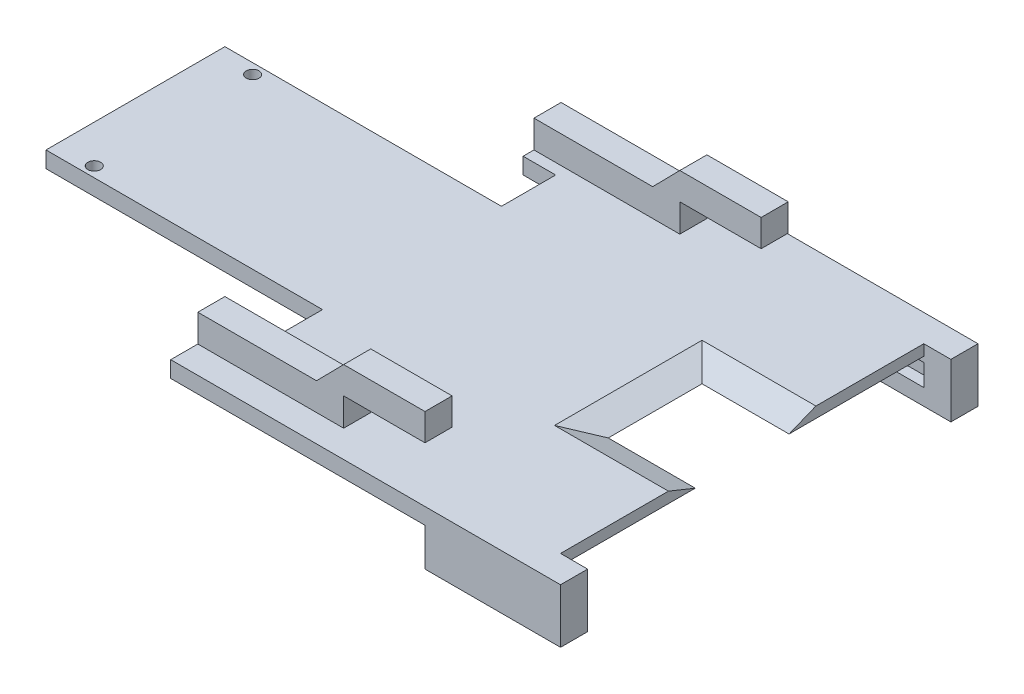
SolidWorks part; units mm, degrees
ref_plane "Front Plane" through (0, 0, 0) normal (0, 0, 1) x (1, 0, 0)
ref_plane "Top Plane" through (0, 0, 0) normal (0, 1, 0) x (1, 0, 0)
ref_plane "Right Plane" through (0, 0, 0) normal (1, 0, 0) x (0, 0, -1)
sketch "Sketch1" plane through (0, 0, 0) normal (0, 0, 1) x (1, 0, 0)
  line L1 (0, 0) -> (31.75, 0)
  line L2 (0, 0) -> (0, 12.7)
  line L3 (0, 12.7) -> (31.75, 12.7)
  line L4 (31.75, 0) -> (31.75, 12.7)
  dimension "D1" = 12.7
  dimension "D2" = 31.75
extrude "Boss-Extrude1" add sketch "Sketch1" along normal blind 6.35
sketch "Sketch3" plane through (0, 0, 6.35) normal (0, 0, 1) x (1, 0, 0)
  line L0 (0, 6.35) -> (25.4, 6.35) construction
  line L1 (0, 12.7) -> (0, 0) construction
  line L4 (25.4, 8.89) -> (0, 8.89)
  line L5 (25.4, 8.89) -> (25.4, 3.81)
  line L6 (25.4, 3.81) -> (0, 3.81)
  line L7 (0, 8.89) -> (0, 3.81)
  dimension "D1" = 25.4
  dimension "D2" = 2.54
  dimension "D3" = 5.08
extrude "Cut-Extrude1" cut sketch "Sketch3" against normal blind 2.54
sketch "Sketch4" plane through (0, 12.7, 0) normal (0, 1, 0) x (1, 0, 0)
  line L0 (0, 0) -> (-25.4, 0)
  line L1 (0, -6.35) -> (-19.05, -6.35)
  line L2 (-25.4, 0) -> (-25.4, -97.79)
  line L3 (-25.4, -97.79) -> (31.75, -97.79)
  line L4 (31.75, -97.79) -> (31.75, -91.44)
  line L5 (31.75, -91.44) -> (-19.05, -91.44)
  line L6 (-19.05, -91.44) -> (-19.05, -6.35)
  line L7 (0, -6.35) -> (0, 0)
  dimension "D1" = 25.4
  dimension "D2" = 97.79
  dimension "D3" = 50.8
  dimension "D4" = 19.05
  dimension "D5" = 6.35
extrude "Boss-Extrude2" add sketch "Sketch4" against normal up to surface (3.81 mm away) up to face at (12.7, 8.89, 5.08)
sketch "Sketch5" plane through (0, 8.89, 0) normal (0, -1, 0) x (1, 0, 0)
  line L0 (-19.05, 91.44) -> (31.75, 91.44) construction
  line L1 (31.75, 97.79) -> (0, 97.79)
  line L2 (31.75, 97.79) -> (31.75, 91.44)
  line L3 (31.75, 91.44) -> (0, 91.44)
  line L4 (0, 97.79) -> (0, 91.44)
extrude "Boss-Extrude3" add sketch "Sketch5" along normal up to surface (8.89 mm away) up to face at (15.875, 0, 3.175)
sketch "Sketch6" plane through (0, 0, 91.44) normal (0, 0, -1) x (-1, 0, 0)
  line L0 (0, 0) -> (0, 3.81) construction
  line L1 (0, 0) -> (0, 8.89) construction
  line L2 (0, 8.89) -> (-3.0339, 8.89) construction
  line L4 (0, 3.81) -> (-25.4, 3.81)
  line L5 (0, 3.81) -> (0, 8.89)
  line L6 (0, 8.89) -> (-25.4, 8.89)
  line L7 (-25.4, 3.81) -> (-25.4, 8.89)
  dimension "D1" = 5.08
extrude "Cut-Extrude2" cut sketch "Sketch6" against normal blind 2.54
sketch "Sketch9" plane through (-25.4, 0, 0) normal (-1, 0, 0) x (0, 0, 1)
  line L0 (0, 12.7) -> (6.35, 12.7) construction
  line L1 (0, 12.7) -> (97.79, 12.7) construction
  line L2 (97.79, 12.7) -> (91.44, 12.7) construction
  line L3 (97.79, 8.89) -> (0, 8.89) construction
  line L4 (91.44, 12.7) -> (85.09, 12.7)
  line L5 (91.44, 12.7) -> (91.44, 8.89)
  line L6 (91.44, 8.89) -> (85.09, 8.89)
  line L7 (85.09, 12.7) -> (85.09, 8.89)
  line L9 (6.35, 12.7) -> (12.7, 12.7)
  line L10 (6.35, 12.7) -> (6.35, 8.89)
  line L11 (6.35, 8.89) -> (12.7, 8.89)
  line L12 (12.7, 12.7) -> (12.7, 8.89)
  dimension "D1" = 6.35
  dimension "D2" = 6.35
  dimension "D3" = 6.35
  dimension "D4" = 6.35
extrude "Boss-Extrude5" add sketch "Sketch9" along normal blind 6.35
sketch "Sketch10" plane through (0, 12.7, 0) normal (0, 1, 0) x (1, 0, 0)
  line L1 (-31.75, -85.09) -> (-25.4, -85.09)
  line L2 (-31.75, -85.09) -> (-31.75, -91.44)
  line L3 (-31.75, -91.44) -> (-25.4, -91.44)
  line L4 (-25.4, -85.09) -> (-25.4, -91.44)
  line L5 (-31.75, -6.35) -> (-25.4, -6.35)
  line L6 (-31.75, -6.35) -> (-31.75, -12.7)
  line L7 (-31.75, -12.7) -> (-25.4, -12.7)
  line L8 (-25.4, -6.35) -> (-25.4, -12.7)
extrude "Boss-Extrude6" add sketch "Sketch10" along normal blind 12.9159
sketch "Sketch12" plane through (-25.4, 0, 0) normal (-1, 0, 0) x (0, 0, 1)
  line L1 (97.79, 8.89) -> (91.44, 8.89)
  line L2 (97.79, 8.89) -> (97.79, 12.7)
  line L3 (97.79, 12.7) -> (91.44, 12.7)
  line L4 (91.44, 8.89) -> (91.44, 12.7)
  line L5 (0, 8.89) -> (6.35, 8.89)
  line L6 (0, 8.89) -> (0, 12.7)
  line L7 (0, 12.7) -> (6.35, 12.7)
  line L8 (6.35, 8.89) -> (6.35, 12.7)
extrude "Boss-Extrude8" add sketch "Sketch12" along normal blind 6.35
sketch "Sketch14" plane through (-25.4, 0, 0) normal (1, 0, 0) x (0, 0, -1)
  line L0 (-85.09, 25.6159) -> (-85.09, 12.7) construction
  line L1 (-91.44, 25.6159) -> (-85.09, 25.6159)
  line L2 (-91.44, 25.6159) -> (-91.44, 19.2659)
  line L3 (-91.44, 19.2659) -> (-85.09, 19.2659)
  line L4 (-85.09, 25.6159) -> (-85.09, 19.2659)
  line L6 (-12.7, 25.6159) -> (-6.35, 25.6159)
  line L7 (-12.7, 25.6159) -> (-12.7, 19.2659)
  line L8 (-12.7, 19.2659) -> (-6.35, 19.2659)
  line L9 (-6.35, 25.6159) -> (-6.35, 19.2659)
  dimension "D1" = 6.35
  dimension "D2" = 6.35
extrude "Boss-Extrude11" add sketch "Sketch14" along normal blind 19.05
sketch "Sketch18" plane through (0, 0, 91.44) normal (0, 0, 1) x (1, 0, 0)
  line L0 (-31.75, 19.1579) -> (-25.4, 25.6159)
  line L1 (-31.75, 12.7) -> (-31.75, 25.6159) construction
  line L3 (-25.4, 25.6159) -> (-31.75, 25.6159)
  line L4 (-31.75, 25.6159) -> (-31.75, 19.1579)
  dimension "D1" = 6.35
extrude "Cut-Extrude9" cut sketch "Sketch18" against normal through all
sketch "Sketch19" plane through (-25.4, 0, 0) normal (-1, 0, 0) x (0, 0, 1)
  line L0 (12.7, 12.7) -> (85.09, 12.7) construction
  line L1 (12.7, 8.89) -> (85.09, 8.89)
  line L2 (12.7, 8.89) -> (12.7, 12.7)
  line L3 (12.7, 12.7) -> (85.09, 12.7)
  line L4 (85.09, 8.89) -> (85.09, 12.7)
extrude "Boss-Extrude12" add sketch "Sketch19" along normal blind 34.163
sketch "Sketch20" plane through (-31.75, 0, 0) normal (-1, 0, 0) x (0, 0, 1)
  line L0 (0, 8.89) -> (0, 12.7)
  line L1 (0, 12.7) -> (6.35, 12.7)
  line L2 (6.35, 12.7) -> (6.35, 19.1579)
  line L3 (6.35, 19.1579) -> (12.7, 19.1579)
  line L4 (12.7, 19.1579) -> (12.7, 8.89)
  line L5 (12.7, 8.89) -> (0, 8.89)
  line L6 (85.09, 19.1579) -> (91.44, 19.1579)
  line L7 (91.44, 19.1579) -> (91.44, 12.7)
  line L8 (91.44, 12.7) -> (97.79, 12.7)
  line L9 (97.79, 12.7) -> (97.79, 8.89)
  line L10 (97.79, 8.89) -> (85.09, 8.89)
  line L11 (85.09, 8.89) -> (85.09, 19.1579)
extrude "Boss-Extrude13" add sketch "Sketch20" along normal up to surface (27.813 mm away) up to face at (-59.563, 10.795, 48.895)
sketch "Sketch21" plane through (-59.563, 0, 0) normal (-1, 0, 0) x (0, 0, 1)
  line L0 (0, 8.89) -> (15.24, 8.89) construction
  line L1 (0, 8.89) -> (97.79, 8.89) construction
  line L2 (97.79, 8.89) -> (82.55, 8.89) construction
  line L3 (85.09, 12.7) -> (12.7, 12.7) construction
  line L4 (15.24, 8.89) -> (27.94, 8.89)
  line L5 (15.24, 8.89) -> (15.24, 12.7)
  line L6 (15.24, 12.7) -> (27.94, 12.7)
  line L7 (27.94, 8.89) -> (27.94, 12.7)
  line L9 (82.55, 8.89) -> (69.85, 8.89)
  line L10 (82.55, 8.89) -> (82.55, 12.7)
  line L11 (82.55, 12.7) -> (69.85, 12.7)
  line L12 (69.85, 8.89) -> (69.85, 12.7)
  dimension "D1" = 12.7
  dimension "D2" = 15.24
  dimension "D3" = 12.7
  dimension "D4" = 15.24
extrude "Cut-Extrude10" cut sketch "Sketch21" against normal blind 7.62
sketch "Sketch22" plane through (-59.563, 0, 0) normal (-1, 0, 0) x (0, 0, 1)
  line L1 (27.94, 12.7) -> (69.85, 12.7)
  line L2 (27.94, 12.7) -> (27.94, 8.89)
  line L3 (27.94, 8.89) -> (69.85, 8.89)
  line L4 (69.85, 12.7) -> (69.85, 8.89)
extrude "Boss-Extrude14" add sketch "Sketch22" along normal blind 50.8
sketch "Sketch23" plane through (-19.05, 0, 0) normal (1, 0, 0) x (0, 0, -1)
  line L1 (-6.35, 8.89) -> (-91.44, 8.89)
  line L2 (-6.35, 8.89) -> (-6.35, 12.7)
  line L3 (-6.35, 12.7) -> (-91.44, 12.7)
  line L4 (-91.44, 8.89) -> (-91.44, 12.7)
extrude "Boss-Extrude15" add sketch "Sketch23" along normal blind 44.45
sketch "Sketch24" plane through (0, 8.89, 0) normal (0, -1, 0) x (1, 0, 0)
  line L0 (-110.363, 48.895) -> (-107.823, 48.895) construction
  line L1 (-110.363, 27.94) -> (-110.363, 69.85) construction
  line L2 (-107.823, 48.895) -> (-107.823, 67.437) construction
  line L3 (-107.823, 48.895) -> (-107.823, 30.353) construction
  circle A0 centre (-107.823, 30.353) radius 1.5
  circle A1 centre (-107.823, 67.437) radius 1.5
  dimension "D4" = 3
  dimension "D5" = 3
  dimension "D1" = 2.54
  dimension "D2" = 18.542
  dimension "D3" = 18.542
extrude "Cut-Extrude11" cut sketch "Sketch24" against normal through all
sketch "Sketch25" plane through (-110.363, 0, 0) normal (-1, 0, 0) x (0, 0, 1)
  line L1 (69.85, 12.7) -> (27.94, 12.7)
  line L2 (69.85, 12.7) -> (69.85, 8.89)
  line L3 (69.85, 8.89) -> (27.94, 8.89)
  line L4 (27.94, 12.7) -> (27.94, 8.89)
extrude "Boss-Extrude16" add sketch "Sketch25" along normal blind 6.35
sketch "Sketch26" plane through (0, 8.89, 0) normal (0, -1, 0) x (1, 0, 0)
  line L0 (25.4, 48.895) -> (25.4, 37.973)
  line L1 (25.4, 91.44) -> (25.4, 6.35) construction
  line L2 (25.4, 48.895) -> (25.4, 59.817)
  line L4 (25.4, 37.973) -> (5.08, 37.973)
  line L5 (25.4, 37.973) -> (25.4, 59.817)
  line L6 (25.4, 59.817) -> (5.08, 59.817)
  line L7 (5.08, 37.973) -> (5.08, 59.817)
  line M12 (25.4, 6.35) -> (25.4, 91.44)
  dimension "D1" = 10.922
  dimension "D2" = 20.32
extrude "Cut-Extrude12" cut sketch "Sketch26" against normal through all both and the other way through all contours L7 L4 L6 M12 region at (15.24, 8.89, 48.895)
sketch "Sketch27" plane through (0, 8.89, 0) normal (0, -1, 0) x (1, 0, 0)
  line L0 (25.4, 37.973) -> (25.4, 6.35)
  line L1 (25.4, 6.35) -> (-38.1, 6.35)
  line L2 (25.4, 37.973) -> (5.08, 37.973)
  line L3 (5.08, 37.973) -> (5.08, 59.817)
  line L4 (5.08, 59.817) -> (25.4, 59.817)
  line L5 (25.4, 59.817) -> (25.4, 91.44)
  line L6 (25.4, 91.44) -> (-38.1, 91.44)
  line L7 (-38.1, 91.44) -> (-38.1, 6.35)
  dimension "D1" = 63.5
extrude "Cut-Extrude13" cut sketch "Sketch27" against normal blind 1.27
chamfer "Chamfer1" distance 6.35 angle 22 3 edges at (15.24, 12.7, 59.817) (5.08, 12.7, 48.895) (15.24, 12.7, 37.973) first distance on face at (-107.823, 12.7, 28.853)
